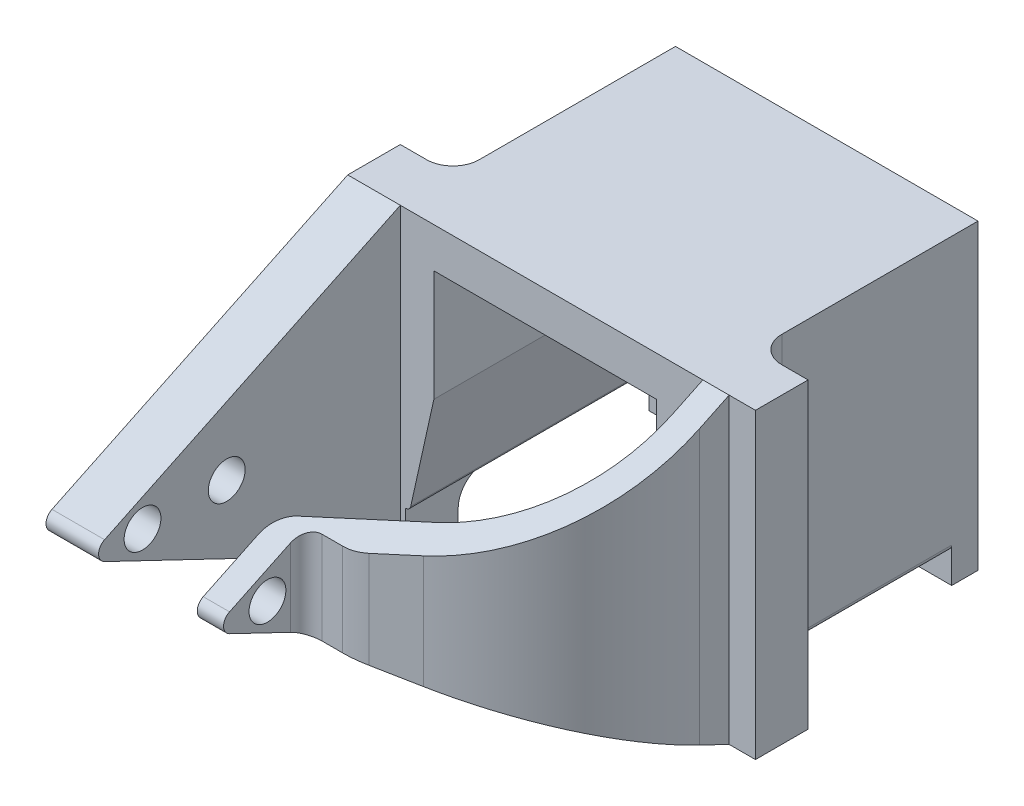
SolidWorks part; units mm, degrees
ref_plane "Front Plane" through (0, 0, 0) normal (0, 0, 1) x (1, 0, 0)
ref_plane "Top Plane" through (0, 0, 0) normal (0, 1, 0) x (1, 0, 0)
ref_plane "Right Plane" through (0, 0, 0) normal (1, 0, 0) x (0, 0, -1)
sketch "Sketch2" plane through (0, 0, 0) normal (0, 0, 1) x (1, 0, 0)
  line L1 (0, 0) -> (57.5, 0)
  line L2 (0, 0) -> (0, 57.5)
  line L3 (0, 57.5) -> (57.5, 57.5)
  line L4 (57.5, 0) -> (57.5, 57.5)
  dimension "D1" = 57.5
  dimension "D2" = 57.5
extrude "Boss-Extrude1" add sketch "Sketch2" along normal blind 5
sketch "Sketch3" plane through (0, 0, 5) normal (0, 0, 1) x (1, 0, 0)
  line L0 (57.5, 57.5) -> (0, 57.5) construction
  line L1 (6.3759, 7.6) -> (48.6759, 7.6)
  line L2 (6.3759, 7.6) -> (6.3759, 49.9)
  line L3 (6.3759, 49.9) -> (48.6759, 49.9)
  line L4 (48.6759, 7.6) -> (48.6759, 49.9)
  line L5 (0, 57.5) -> (0, 0) construction
  line L6 (57.5, 0) -> (57.5, 57.5) construction
  line L7 (0, 0) -> (57.5, 0) construction
  line L8 (0, 57.5) -> (0, 0)
  line L9 (57.5, 57.5) -> (0, 57.5)
  line L10 (57.5, 0) -> (57.5, 57.5)
  line L11 (0, 0) -> (57.5, 0)
  dimension "D1" = 42.3
  dimension "D2" = 42.3
  dimension "D3" = 7.6
  dimension "D4" = 6.3759
extrude "Boss-Extrude2" add sketch "Sketch3" along normal blind 47.3
sketch "Sketch4" plane through (0, 0, 0) normal (-1, 0, 0) x (0, 0, 1)
  line L0 (52.3, 57.5) -> (0, 57.5) construction
  line L1 (42.3, 57.5) -> (112.3, 57.5)
  line L2 (42.3, 57.5) -> (42.3, 0)
  line L3 (42.3, 0) -> (112.3, 0)
  line L4 (112.3, 57.5) -> (112.3, 0)
  line L5 (52.3, 57.5) -> (52.3, 0) construction
  dimension "D1" = 10
  dimension "D2" = 60
extrude "Boss-Extrude3" add sketch "Sketch4" along normal blind 10
sketch "Sketch5" plane through (57.5, 0, 0) normal (1, 0, 0) x (0, 0, -1)
  line L0 (-52.3, 0) -> (0, 0) construction
  line L1 (-42.3, 0) -> (-112.3, 0)
  line L2 (-42.3, 0) -> (-42.3, 57.5)
  line L3 (-42.3, 57.5) -> (-112.3, 57.5)
  line L4 (-112.3, 0) -> (-112.3, 57.5)
  line L5 (-52.3, 0) -> (-52.3, 57.5) construction
  dimension "D1" = 10
  dimension "D2" = 60
extrude "Boss-Extrude4" add sketch "Sketch5" along normal blind 10
sketch "Sketch6" plane through (57.5, 0, 0) normal (-1, 0, 0) x (0, 0, 1)
  line L0 (52.3, 57.5) -> (112.3, 57.5) construction
  line L1 (77.3, 57.5) -> (112.3, 57.5)
  line L2 (77.3, 57.5) -> (77.3, 0)
  line L3 (77.3, 0) -> (112.3, 0)
  line L4 (112.3, 57.5) -> (112.3, 0)
  line L5 (52.3, 0) -> (52.3, 57.5) construction
  dimension "D1" = 25
extrude "Boss-Extrude5" add sketch "Sketch6" along normal blind 38.75
sketch "Sketch7" plane through (0, 0, 0) normal (1, 0, 0) x (0, 0, -1)
  line L0 (-52.3, 57.5) -> (-52.3, 0) construction
  line L1 (-52.3, 57.5) -> (-52.3, 0) construction
  line L2 (-66.8342, 28.75) -> (-119.0172, 28.75) construction
  circle A0 centre (-101.3, 28.75) radius 3.5
  circle A1 centre (-85.3, 28.75) radius 3.5
  dimension "D1" = 7
  dimension "D3" = 7
  dimension "D2" = 49
  dimension "D4" = 16
extrude "Cut-Extrude1" cut sketch "Sketch7" against normal through all
sketch "Sketch8" plane through (0, 0, 0) normal (1, 0, 0) x (0, 0, -1)
  circle A0 centre (-101.3, 28.75) radius 3.5 construction
  circle A1 centre (-101.3, 28.75) radius 3.5
extrude "Cut-Extrude2" cut sketch "Sketch8" along normal through all
fillet "Fillet1" radius 30 4 edges at (-5, 57.5, 112.3) (43.125, 57.5, 112.3) (43.125, 0, 112.3) (-5, 0, 112.3)
sketch "Sketch9" plane through (0, 0, 0) normal (0, -1, 0) x (1, 0, 0)
  line L2 (18.75, 77.3) -> (18.75, 94.8)
  line L3 (18.75, 112.2739) -> (18.75, 82.3) construction
  line L4 (18.75, 94.8) -> (57.5, 77.3)
  line L5 (57.5, 77.3) -> (18.75, 77.3)
  dimension "D1" = 17.5
extrude "Cut-Extrude3" cut sketch "Sketch9" against normal through all
sketch "Sketch10" plane through (0, 0, 52.3) normal (0, 0, 1) x (1, 0, 0)
  line L8 (6.3759, 28.75) -> (0, 0)
  line L9 (0, 0) -> (57.5, 0)
  line L10 (57.5, 0) -> (48.6759, 28.75)
  line L11 (48.6759, 28.75) -> (6.3759, 28.75)
extrude "Cut-Extrude4" cut sketch "Sketch10" against normal up to surface (47.3 mm away) up to face at (27.5259, 28.75, 5)
sketch "Sketch11" plane through (67.5, 0, 0) normal (1, 0, 0) x (0, 0, -1)
  line L2 (-112.2739, 28.75) -> (-52.3, 57.5)
  line L3 (-112.2739, 28.75) -> (-52.3, 0)
  line L4 (-42.3, 57.5) -> (-82.3, 57.5) construction
  line L5 (-82.3, 0) -> (-42.3, 0) construction
  line L6 (-52.3, 57.5) -> (-82.3, 57.5)
  line L7 (-82.3, 0) -> (-52.3, 0)
  arc A0 (-82.3, 57.5) -> (-112.2739, 28.75) centre (-82.3, 27.5) ccw construction
  arc A1 (-112.2739, 28.75) -> (-82.3, 0) centre (-82.3, 30) ccw construction
  arc A2 (-82.3, 57.5) -> (-112.2739, 28.75) centre (-82.3, 27.5) ccw
  arc A3 (-112.2739, 28.75) -> (-82.3, 0) centre (-82.3, 30) ccw
  line M4 (-42.3, 57.5) -> (-82.3, 57.5)
  arc M5 (-82.3, 57.5) -> (-112.2739, 28.75) centre (-82.3, 27.5) ccw
  arc M6 (-112.2739, 28.75) -> (-82.3, 0) centre (-82.3, 30) ccw
  line M7 (-82.3, 0) -> (-42.3, 0)
extrude "Cut-Extrude5" cut sketch "Sketch11" against normal through all contours L2 M5 M4 | L3 M6 M7 region at (67.5, 47.0798, 88.4651) region at (67.5, 10.4202, 88.4651)
fillet "Fillet4" radius 2 2 edges at (-5, 28.75, 112.2739) (43.125, 28.75, 112.2739)
fillet "Fillet5" radius 30 1 edges
fillet "Fillet6" radius 5 1 edges at (18.75, 28.75, 94.8)
sketch "Sketch12" plane through (0, 0, 0) normal (0, -1, 0) x (1, 0, 0)
  line L1 (-10, 52.3) -> (1, 52.3)
  line L2 (-10, 52.3) -> (-10, 42.3)
  line L3 (-10, 42.3) -> (1, 42.3)
  line L4 (1, 52.3) -> (1, 42.3)
  line L5 (67.5, 52.3) -> (56.5, 52.3)
  line L6 (67.5, 52.3) -> (67.5, 42.3)
  line L7 (67.5, 42.3) -> (56.5, 42.3)
  line L8 (56.5, 52.3) -> (56.5, 42.3)
  dimension "D1" = 11
  dimension "D2" = 11
extrude "Boss-Extrude6" add sketch "Sketch12" against normal blind 10
fillet "Fillet7" radius 1 2 edges tangent propagation no
fillet "Fillet8" radius 5 4 edges at (0.2929, 8.4208, 42.3) (57.2071, 5.9591, 42.3)
sketch "Sketch13" plane through (0, 0, 0) normal (0, -1, 0) x (1, 0, 0)
  line L0 (32.8278, 93.9285) -> (23.75, 93.9285)
  line L1 (23.75, 93.9285) -> (23.75, 98.0282)
  line L3 (23.75, 108.5118) -> (23.75, 111.8235)
  line L17 (23.75, 111.8235) -> (71.5069, 111.8235)
  line L18 (71.5069, 111.8235) -> (71.5069, 52.3)
  line L19 (62.5, 57.9309) -> (62.5, 52.3)
  line L20 (32.8278, 93.9285) -> (41.9055, 89.8289)
  line L21 (23.75, 98.0282) -> (23.75, 108.5118)
  line L22 (71.5069, 52.3) -> (62.5, 52.3)
  arc A8 (62.5, 57.9309) -> (41.9055, 89.8289) centre (27.5, 57.9309) ccw
extrude "Cut-Extrude6" cut sketch "Sketch13" against normal through all
fillet "Fillet10" radius 3 1 edges at (23.75, 28.75, 93.9285)
fillet "Fillet11" radius 10 1 edges at (32.8278, 28.75, 93.9285)
sketch "Sketch14" plane through (57.5, 0, 0) normal (1, 0, 0) x (0, 0, -1)
  line L0 (-37.3, 57.5) -> (0, 57.5) construction
  line L1 (-37.3, 57.5) -> (0, 57.5) construction
